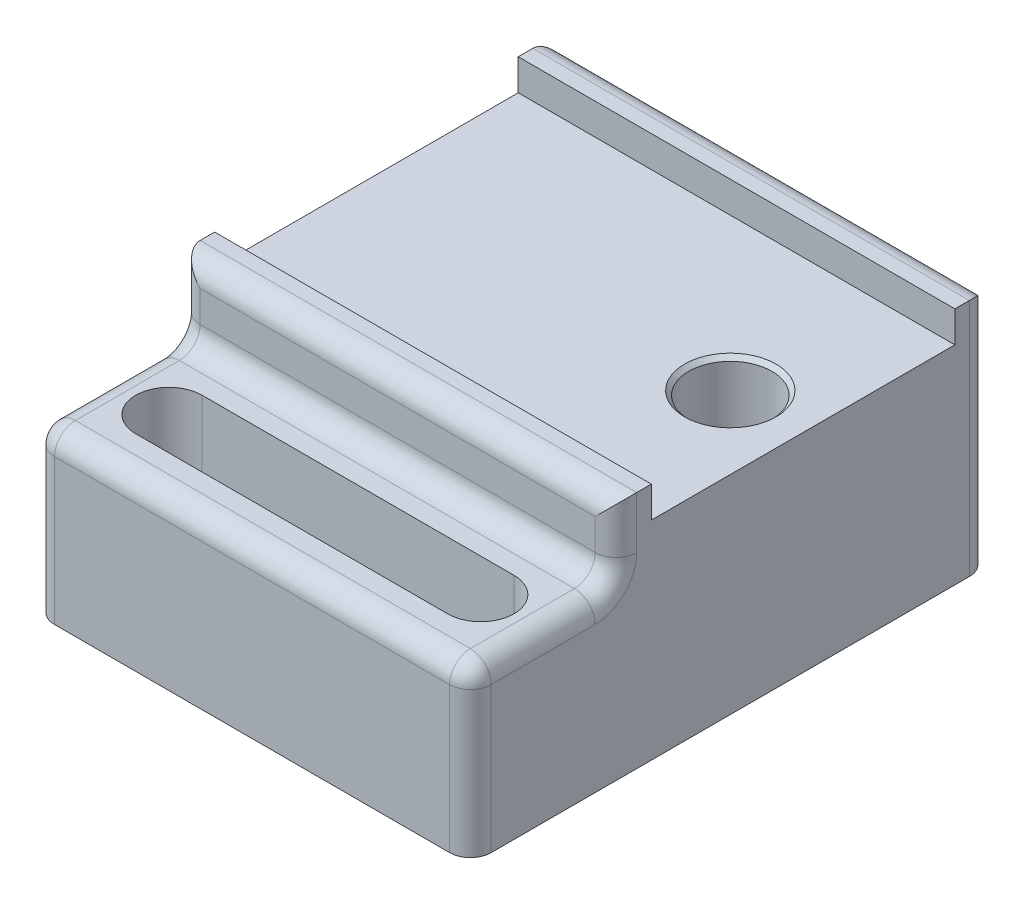
SolidWorks part; units mm, degrees
ref_plane "Front Plane" through (0, 0, 0) normal (0, 0, 1) x (1, 0, 0)
ref_plane "Top Plane" through (0, 0, 0) normal (0, 1, 0) x (1, 0, 0)
ref_plane "Right Plane" through (0, 0, 0) normal (1, 0, 0) x (0, 0, -1)
sketch "Sketch1" plane through (0, 0, 0) normal (0, 1, 0) x (1, 0, 0)
  line L1 (-10.5, 7.3) -> (10.5, 7.3)
  line L2 (-10.5, 7.3) -> (-10.5, -7.3)
  line L3 (-10.5, -7.3) -> (10.5, -7.3)
  line L4 (10.5, 7.3) -> (10.5, -7.3)
  line L5 (-10.5, 7.3) -> (10.5, -7.3) construction
  line L6 (-10.5, -7.3) -> (10.5, 7.3) construction
  line L7 (-10.5, 9) -> (10.5, 9)
  line L8 (-10.5, 9) -> (-10.5, -9)
  line L9 (-10.5, -9) -> (10.5, -9)
  line L10 (10.5, 9) -> (10.5, -9)
  line L11 (-10.5, 9) -> (10.5, -9) construction
  line L12 (-10.5, -9) -> (10.5, 9) construction
  point P0 (0, 0)
  point P6 (0, 0)
  dimension "D1" = 21
  dimension "D2" = 14.6
  dimension "D3" = 18
extrude "Boss-Extrude1" add sketch "Sketch1" along normal blind 10 contours L4 L1 L2 L3 region at (0, 0, 0)
extrude "Boss-Extrude2" add sketch "Sketch1<3>" along normal blind 11.5 contours L10 L3 L8 L9 | L10 L7 L8 L1 region at (0, 0, -8.15) region at (0, 0, 8.15)
sketch "Sketch1<3>" plane through (0, 0, 0) normal (0, 1, 0) x (1, 0, 0) same geometry as "Sketch1"
sketch "Sketch3" plane through (0, 0, 0) normal (0, 1, 0) x (1, 0, 0)
  line L1 (-10.5, -9) -> (10.5, -9)
  line L2 (-10.5, -9) -> (-10.5, -16)
  line L3 (-10.5, -16) -> (10.5, -16)
  line L4 (10.5, -9) -> (10.5, -16)
  dimension "D1" = 7
extrude "Boss-Extrude4" add sketch "Sketch3" along normal blind 8
fillet "Fillet1" radius 1 12 edges at (10.5, 8, 12.5) (-10.5, 9.75, 9) (10.5, 5.75, -9) (0, 11.5, 9) (-10.5, 5.75, -9) (0, 11.5, -9) (-10.5, 4, 16) (10.5, 4, 16) (0, 8, 16) (10.5, 9.75, 9) (-10.5, 8, 12.5) (0, 8, 9)
sketch "Sketch4" plane through (0, 8, 0) normal (0, 1, 0) x (1, 0, 0)
  line L0 (-9.5, -12.5) -> (9.5, -12.5) construction
  line L1 (-9.5, -10) -> (-9.5, -15) construction
  line L2 (9.5, -15) -> (9.5, -10) construction
  line L3 (-7.5, -12.5) -> (7.5, -12.5) construction
  line L4 (-7.5, -10.9) -> (7.5, -10.9)
  line L5 (-7.5, -14.1) -> (7.5, -14.1)
  arc A0 (-7.5, -10.9) -> (-7.5, -14.1) centre (-7.5, -12.5) ccw
  arc A1 (7.5, -14.1) -> (7.5, -10.9) centre (7.5, -12.5) ccw
  point P8 (0, -12.5)
  dimension "D3" = 1.6
  dimension "D1" = 2
  dimension "D2" = 2
extrude "Cut-Extrude1" cut sketch "Sketch4" against normal through all
sketch "Sketch5" plane through (0, 10, 0) normal (0, 1, 0) x (1, 0, 0)
  line L0 (10.5, 7.3) -> (10.5, -7.3) construction
  circle A0 centre (7, 0) radius 2
  point P2 (0, 0)
  point P6 (0, 0)
  dimension "D1" = 4
  dimension "D2" = 3.5
extrude "Cut-Extrude2" cut sketch "Sketch5" against normal blind 6.8
chamfer "Chamfer1" distance 0.2 angle 45 1 edges at (7, 10, 2)
